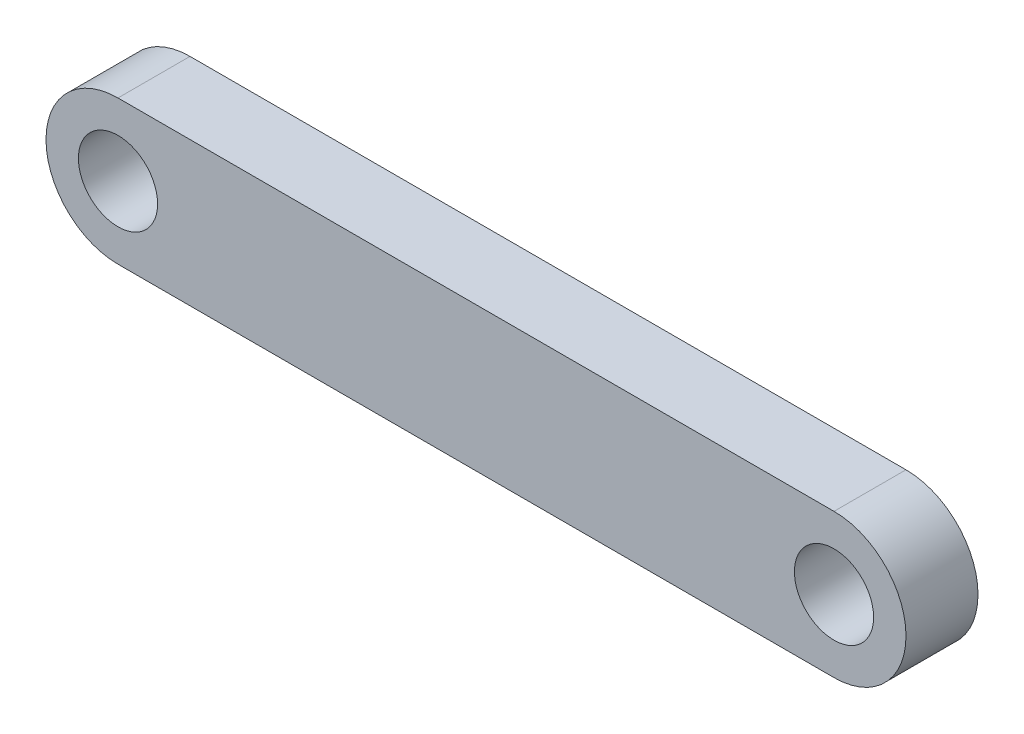
SolidWorks part; units mm, degrees
ref_plane "Front Plane" through (0, 0, 0) normal (0, 0, 1) x (1, 0, 0)
ref_plane "Top Plane" through (0, 0, 0) normal (0, 1, 0) x (1, 0, 0)
ref_plane "Right Plane" through (0, 0, 0) normal (1, 0, 0) x (0, 0, -1)
sketch "Sketch1" plane through (0, 0, 0) normal (0, 0, 1) x (1, 0, 0)
  line L0 (-14.9171, 3.0494) -> (14.9171, 3.0494)
  line L1 (14.9171, -2.9506) -> (-14.9171, -2.9506)
  line L2 (-14.9171, 0.0494) -> (14.9171, 0.0494) construction
  arc A0 (14.9171, -2.9506) -> (14.9171, 3.0494) centre (14.9171, 0.0494) ccw
  arc A1 (-14.9171, 3.0494) -> (-14.9171, -2.9506) centre (-14.9171, 0.0494) ccw
  circle A2 centre (-14.9171, 0.0494) radius 1.65
  circle A3 centre (14.9171, 0.0494) radius 1.65
  point P8 (0, 0)
  point P9 (0, 0.0494)
  point P10 (14.9171, 3.0494)
  dimension "D1" = 6
  dimension "D2" = 3.3
extrude "Boss-Extrude1" add sketch "Sketch1" along normal blind 3
